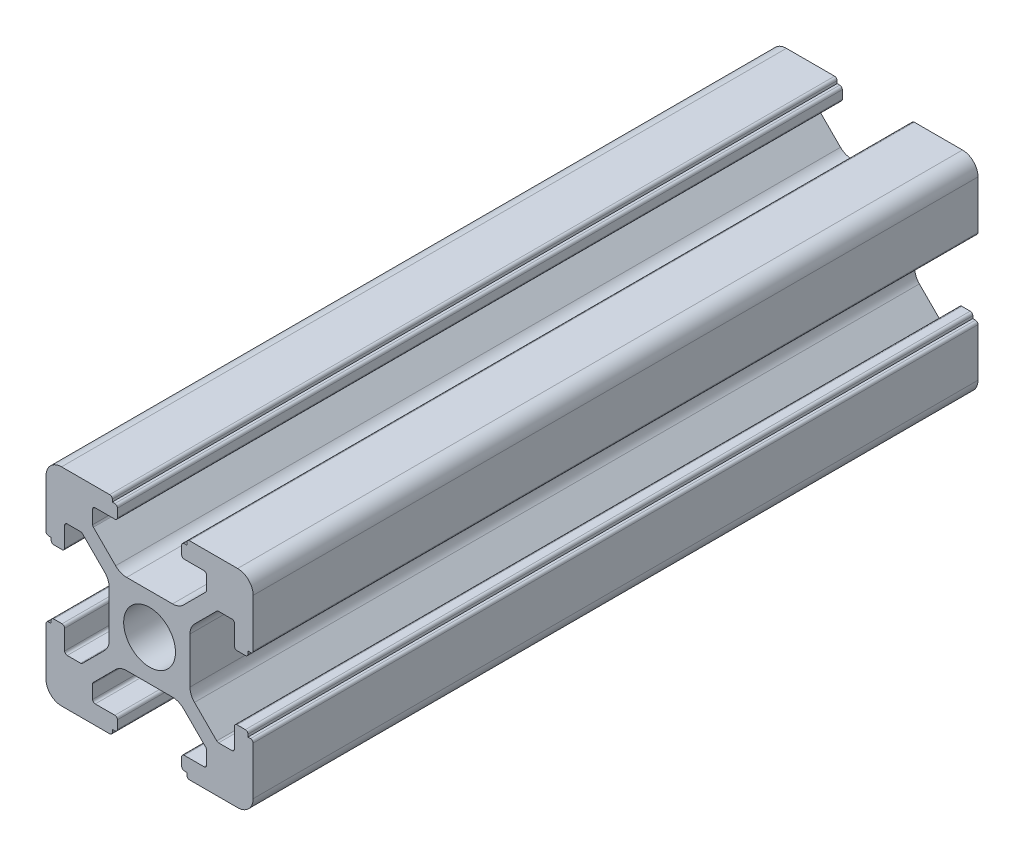
SolidWorks part; units mm, degrees
ref_plane "前视基准面" through (0, 0, 0) normal (0, 0, 1) x (1, 0, 0)
ref_plane "上视基准面" through (0, 0, 0) normal (0, 1, 0) x (1, 0, 0)
ref_plane "右视基准面" through (0, 0, 0) normal (1, 0, 0) x (0, 0, -1)
sketch "草图1" plane through (0, 0, 0) normal (0, 0, 1) x (1, 0, 0)
  line L0 (0, 0) -> (0, 5.5) construction
  line L1 (-8.5023, -10.0023) -> (-3.85, -10.0023)
  line L2 (-10.0023, -8.5023) -> (-10.0023, -3.85)
  line L3 (-8.5023, 10.0023) -> (-3.85, 10.0023)
  line L4 (10.0023, -8.5023) -> (10.0023, -3.85)
  line L5 (-10.0023, -10.0023) -> (10.0023, 10.0023) construction
  line L6 (-10.0023, 10.0023) -> (10.0023, -10.0023) construction
  line L7 (-2.218, -3.9) -> (2.218, -3.9)
  line L8 (-3.9, -2.218) -> (-3.9, 2.218)
  line L9 (-2.218, 3.9) -> (2.218, 3.9)
  line L10 (3.9, -2.218) -> (3.9, 2.218)
  line L11 (-3.9, -3.9) -> (3.9, 3.9) construction
  line L12 (-3.9, 3.9) -> (3.9, -3.9) construction
  line L13 (-5.25, -8.2) -> (-3.35, -8.2)
  line L14 (-8.2, -5.25) -> (-8.2, -3.35)
  line L15 (-5.25, 8.2) -> (-3.35, 8.2)
  line L16 (8.2, -5.25) -> (8.2, -3.35)
  line L17 (-8.2, -8.2) -> (8.2, 8.2) construction
  line L18 (-8.2, 8.2) -> (8.2, -8.2) construction
  line L19 (-7.95, 5.5) -> (-6.6642, 5.5)
  line L20 (0, 0) -> (5.5, 0) construction
  line L23 (-5.5, 7.95) -> (-5.5, 6.6642)
  line L26 (0, 0) -> (-0.5303, 0.5303)
  line L27 (3.2787, 4.3393) -> (5.4268, 6.4874)
  line L28 (0, 0) -> (0.5303, -0.5303)
  line L29 (5.5, 6.6642) -> (5.5, 7.95)
  line L30 (4.3393, 3.2787) -> (6.4874, 5.4268)
  line L31 (6.6642, 5.5) -> (7.95, 5.5)
  line L32 (4.3393, -3.2787) -> (6.4874, -5.4268)
  line L33 (3.2787, -4.3393) -> (5.4268, -6.4874)
  line L34 (-3.2787, -4.3393) -> (-5.4268, -6.4874)
  line L35 (-4.3393, -3.2787) -> (-6.4874, -5.4268)
  line L36 (-4.3393, 3.2787) -> (-6.4874, 5.4268)
  line L37 (-3.2787, 4.3393) -> (-5.4268, 6.4874)
  line L38 (3.1, -8.45) -> (3.1, -9.2523)
  line L39 (8.45, 3.1) -> (9.2523, 3.1)
  line L40 (-5.5, -6.6642) -> (-5.5, -7.95)
  line L41 (-6.6642, -5.5) -> (-7.95, -5.5)
  line L42 (5.5, -6.6642) -> (5.5, -7.95)
  line L43 (6.6642, -5.5) -> (7.95, -5.5)
  line L44 (9.2523, -3.1) -> (8.45, -3.1)
  line L46 (10.0023, 3.85) -> (10.0023, 8.5023)
  line L47 (8.2, 3.35) -> (8.2, 5.25)
  line L48 (-3.1, -9.2523) -> (-3.1, -8.45)
  line L49 (-8.45, -3.1) -> (-9.2523, -3.1)
  line L50 (-9.2523, 3.1) -> (-8.45, 3.1)
  line L51 (-3.1, 8.45) -> (-3.1, 9.2523)
  line L52 (3.1, 9.2523) -> (3.1, 8.45)
  line L53 (3.85, 10.0023) -> (8.5023, 10.0023)
  line L54 (3.35, 8.2) -> (5.25, 8.2)
  line L55 (-10.0023, 3.85) -> (-10.0023, 8.5023)
  line L56 (-8.2, 3.35) -> (-8.2, 5.25)
  line L57 (3.35, -8.2) -> (5.25, -8.2)
  line L58 (3.85, -10.0023) -> (8.5023, -10.0023)
  line L59 (9.7523, -3.6) -> (9.5023, -3.6)
  line L61 (9.7523, 3.6) -> (9.5023, 3.6)
  line L62 (9.5023, -3.6) -> (9.5023, -3.35)
  line L63 (3.6, -9.7523) -> (3.6, -9.5023)
  line L64 (3.35, -9.5023) -> (3.6, -9.5023)
  line L65 (9.5023, 3.35) -> (9.5023, 3.6)
  line L66 (-3.6, -9.5023) -> (-3.35, -9.5023)
  line L67 (-3.6, -9.7523) -> (-3.6, -9.5023)
  line L68 (-9.7523, -3.6) -> (-9.5023, -3.6)
  line L69 (-9.5023, -3.35) -> (-9.5023, -3.6)
  line L70 (-9.5023, 3.6) -> (-9.5023, 3.35)
  line L71 (-9.7523, 3.6) -> (-9.5023, 3.6)
  line L72 (-3.6, 9.7523) -> (-3.6, 9.5023)
  line L73 (-3.35, 9.5023) -> (-3.6, 9.5023)
  line L74 (3.6, 9.5023) -> (3.35, 9.5023)
  line L75 (3.6, 9.7523) -> (3.6, 9.5023)
  circle A0 centre (0, 0) radius 2.5
  arc A1 (10.0023, 8.5023) -> (8.5023, 10.0023) centre (8.5023, 8.5023) ccw
  arc A2 (8.5023, -10.0023) -> (10.0023, -8.5023) centre (8.5023, -8.5023) ccw
  arc A3 (-10.0023, -8.5023) -> (-8.5023, -10.0023) centre (-8.5023, -8.5023) ccw
  arc A4 (-10.0023, 8.5023) -> (-8.5023, 10.0023) centre (-8.5023, 8.5023) cw
  arc A5 (-9.5023, -3.35) -> (-9.2523, -3.1) centre (-9.2523, -3.35) cw
  arc A6 (-9.7523, -3.6) -> (-10.0023, -3.85) centre (-9.7523, -3.85) ccw
  arc A7 (-8.45, -3.1) -> (-8.2, -3.35) centre (-8.45, -3.35) cw
  arc A8 (-7.95, -5.5) -> (-8.2, -5.25) centre (-7.95, -5.25) cw
  arc A9 (-6.4874, -5.4268) -> (-6.6642, -5.5) centre (-6.6642, -5.25) cw
  arc A10 (-5.4268, -6.4874) -> (-5.5, -6.6642) centre (-5.25, -6.6642) ccw
  arc A11 (-5.5, -7.95) -> (-5.25, -8.2) centre (-5.25, -7.95) ccw
  arc A12 (-3.6, -9.7523) -> (-3.85, -10.0023) centre (-3.85, -9.7523) cw
  arc A13 (-3.35, -9.5023) -> (-3.1, -9.2523) centre (-3.35, -9.2523) ccw
  arc A14 (-3.1, -8.45) -> (-3.35, -8.2) centre (-3.35, -8.45) ccw
  arc A15 (3.1, -8.45) -> (3.35, -8.2) centre (3.35, -8.45) cw
  arc A16 (5.5, -7.95) -> (5.25, -8.2) centre (5.25, -7.95) cw
  arc A17 (5.4268, -6.4874) -> (5.5, -6.6642) centre (5.25, -6.6642) cw
  arc A18 (6.4874, -5.4268) -> (6.6642, -5.5) centre (6.6642, -5.25) ccw
  arc A19 (7.95, -5.5) -> (8.2, -5.25) centre (7.95, -5.25) ccw
  arc A20 (8.45, -3.1) -> (8.2, -3.35) centre (8.45, -3.35) ccw
  arc A21 (9.5023, -3.35) -> (9.2523, -3.1) centre (9.2523, -3.35) ccw
  arc A22 (9.7523, -3.6) -> (10.0023, -3.85) centre (9.7523, -3.85) cw
  arc A23 (3.35, -9.5023) -> (3.1, -9.2523) centre (3.35, -9.2523) cw
  arc A24 (3.6, -9.7523) -> (3.85, -10.0023) centre (3.85, -9.7523) ccw
  arc A25 (7.95, 5.5) -> (8.2, 5.25) centre (7.95, 5.25) cw
  arc A26 (8.2, 3.35) -> (8.45, 3.1) centre (8.45, 3.35) ccw
  arc A27 (9.5023, 3.35) -> (9.2523, 3.1) centre (9.2523, 3.35) cw
  arc A28 (9.7523, 3.6) -> (10.0023, 3.85) centre (9.7523, 3.85) ccw
  arc A29 (6.6642, 5.5) -> (6.4874, 5.4268) centre (6.6642, 5.25) ccw
  arc A30 (5.4268, 6.4874) -> (5.5, 6.6642) centre (5.25, 6.6642) ccw
  arc A31 (5.5, 7.95) -> (5.25, 8.2) centre (5.25, 7.95) ccw
  arc A32 (3.1, 8.45) -> (3.35, 8.2) centre (3.35, 8.45) ccw
  arc A33 (3.6, 9.7523) -> (3.85, 10.0023) centre (3.85, 9.7523) cw
  arc A34 (3.35, 9.5023) -> (3.1, 9.2523) centre (3.35, 9.2523) ccw
  arc A35 (-9.7523, 3.6) -> (-10.0023, 3.85) centre (-9.7523, 3.85) cw
  arc A36 (-9.5023, 3.35) -> (-9.2523, 3.1) centre (-9.2523, 3.35) ccw
  arc A37 (-8.45, 3.1) -> (-8.2, 3.35) centre (-8.45, 3.35) ccw
  arc A38 (-8.2, 5.25) -> (-7.95, 5.5) centre (-7.95, 5.25) cw
  arc A39 (-6.4874, 5.4268) -> (-6.6642, 5.5) centre (-6.6642, 5.25) ccw
  arc A40 (-5.4268, 6.4874) -> (-5.5, 6.6642) centre (-5.25, 6.6642) cw
  arc A41 (-5.5, 7.95) -> (-5.25, 8.2) centre (-5.25, 7.95) cw
  arc A42 (-3.1, 8.45) -> (-3.35, 8.2) centre (-3.35, 8.45) cw
  arc A43 (-3.1, 9.2523) -> (-3.35, 9.5023) centre (-3.35, 9.2523) ccw
  arc A44 (-3.6, 9.7523) -> (-3.85, 10.0023) centre (-3.85, 9.7523) ccw
  arc A45 (-4.3393, 3.2787) -> (-3.9, 2.218) centre (-5.4, 2.218) cw
  arc A46 (-3.2787, 4.3393) -> (-2.218, 3.9) centre (-2.218, 5.4) ccw
  arc A47 (3.2787, 4.3393) -> (2.218, 3.9) centre (2.218, 5.4) cw
  arc A48 (4.3393, 3.2787) -> (3.9, 2.218) centre (5.4, 2.218) ccw
  arc A49 (4.3393, -3.2787) -> (3.9, -2.218) centre (5.4, -2.218) cw
  arc A50 (3.2787, -4.3393) -> (2.218, -3.9) centre (2.218, -5.4) ccw
  arc A51 (-4.3393, -3.2787) -> (-3.9, -2.218) centre (-5.4, -2.218) ccw
  arc A52 (-2.218, -3.9) -> (-3.2787, -4.3393) centre (-2.218, -5.4) ccw
  point P0 (0, 0)
  point P7 (10.0023, 0)
  point P62 (0, 0)
  point P76 (0, 0)
  point P92 (-8.2, -5.5)
  point P99 (0, 0)
  point P106 (-5.5, -8.2)
  point P117 (5.5, -8.2)
  point P124 (8.2, -5.5)
  point P137 (8.2, 5.5)
  point P140 (8.2, 3.1)
  point P147 (6.5607, 5.5)
  point P152 (5.5, 8.2)
  point P167 (-8.2, 5.5)
  point P174 (-5.5, 8.2)
  dimension "D1" = 1.5
  dimension "D5" = 0.25
  dimension "D6" = 1.5
  dimension "D2" = 4
  dimension "D3" = 4
  dimension "D4" = 4
extrude "凸台-拉伸1" add sketch "草图1" along normal blind 70 contours A52 L7 A50 L33 A17 L42 A16 L57 A15 L38 A23 L64 L63 A24 L58 A2 L4 A22 L59 L62 A21 L44 A20 L16 A19 L43 A18 L32 A49 L10 A48 L30 A29 L31 A25 L47 A26 L39 A27 L65 L61 A28 L46 A1 L53 A33 L75 L74 A34 L52 A32 region at (-9.3629, -9.3629, 0)
